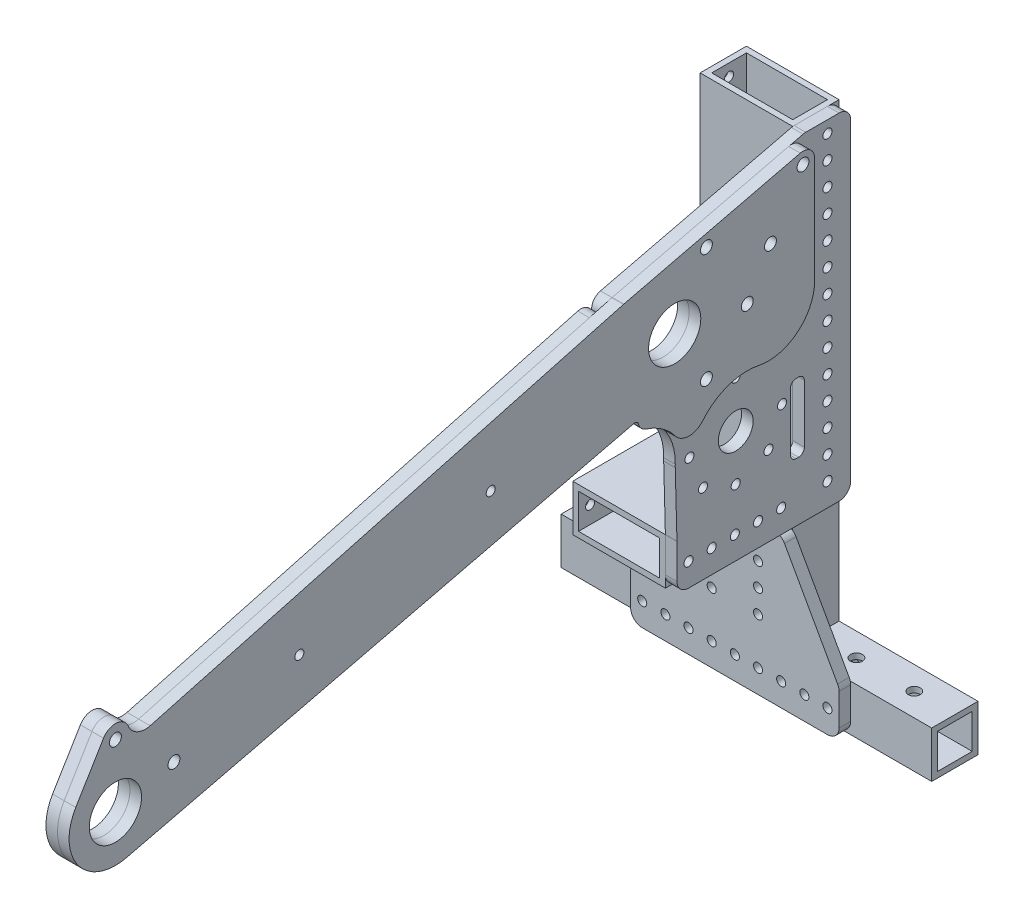
SolidWorks part; units mm, degrees
ref_plane "Alzado" through (0, 0, 0) normal (0, 0, 1) x (1, 0, 0)
ref_plane "Planta" through (0, 0, 0) normal (0, 1, 0) x (1, 0, 0)
ref_plane "Vista lateral" through (0, 0, 0) normal (1, 0, 0) x (0, 0, -1)
sketch "Croquis1" plane through (0, 0, 0) normal (0, 1, 0) x (1, 0, 0)
  line L1 (-101.6, -12.7) -> (101.6, -12.7)
  line L2 (-101.6, -12.7) -> (-101.6, 12.7)
  line L3 (-101.6, 12.7) -> (101.6, 12.7)
  line L4 (101.6, -12.7) -> (101.6, 12.7)
  line L5 (-101.6, -12.7) -> (101.6, 12.7) construction
  line L6 (-101.6, 12.7) -> (101.6, -12.7) construction
  point P0 (0, 0)
  dimension "D1" = 25.4
  dimension "D2" = 203.2
extrude "Saliente-Extruir1" add sketch "Croquis1" along normal blind 25.4
shell "Vaciado1" thickness 3.175 removed face at (-101.6, 12.7, 0) removed face at (101.6, 12.7, 0)
sketch "Croquis2" plane through (0, 25.4, 0) normal (0, 1, 0) x (1, 0, 0)
  line L0 (101.6, 12.7) -> (-101.6, 12.7) construction
  line L1 (-25.4, -12.7) -> (25.4, -12.7)
  line L2 (-25.4, -12.7) -> (-25.4, 12.7)
  line L3 (-25.4, 12.7) -> (25.4, 12.7)
  line L4 (25.4, -12.7) -> (25.4, 12.7)
  line L5 (-25.4, -12.7) -> (25.4, 12.7) construction
  line L6 (-25.4, 12.7) -> (25.4, -12.7) construction
  line L8 (-22.225, -9.525) -> (22.225, -9.525)
  line L9 (-22.225, -9.525) -> (-22.225, 9.525)
  line L10 (-22.225, 9.525) -> (22.225, 9.525)
  line L11 (22.225, -9.525) -> (22.225, 9.525)
  line L12 (-22.225, -9.525) -> (22.225, 9.525) construction
  line L13 (-22.225, 9.525) -> (22.225, -9.525) construction
  point P0 (0, 0)
  point P8 (0, 0)
  dimension "D1" = 50.8
  dimension "D2" = 3.175
  dimension "D3" = 3.175
extrude "Saliente-Extruir2" add sketch "Croquis2" along normal blind 247.65 separate body
sketch "Croquis3" plane through (0, 25.4, 0) normal (0, 1, 0) x (1, 0, 0)
  line L0 (0, 0) -> (0, 12.7) construction
  line L1 (25.4, 12.7) -> (-25.4, 12.7) construction
  circle A0 centre (-47.625, 0) radius 3.2639
  circle A1 centre (-79.375, 0) radius 3.2639
  circle A2 centre (79.375, 0) radius 3.2639
  circle A3 centre (47.625, 0) radius 3.2639
  dimension "D1" = 47.625
  dimension "D2" = 6.5278
  dimension "D3" = 31.75
extrude "Cortar-Extruir1" cut sketch "Croquis3" against normal through all
sketch "Croquis4" plane through (0, 0, 12.7) normal (0, 0, 1) x (1, 0, 0)
  line L0 (0, 25.4) -> (0, 139.6619) construction
  line L1 (-101.6, 25.4) -> (101.6, 25.4) construction
  line L2 (0, 139.6619) -> (-23.8125, 139.6619) construction
  circle A0 centre (0, 139.6619) radius 14.3129
  circle A1 centre (0, 139.6619) radius 23.8125 construction
  circle A2 centre (-23.8125, 139.6619) radius 2.4892 construction
  circle A3 centre (-11.9062, 160.2841) radius 2.4892
  circle A4 centre (11.9063, 160.2841) radius 2.4892
  circle A5 centre (23.8125, 139.6619) radius 2.4892 construction
  circle A6 centre (11.9062, 119.0397) radius 2.4892
  circle A7 centre (-11.9063, 119.0397) radius 2.4892
  dimension "D1" = 28.6258
  dimension "D3" = 47.625
  dimension "D4" = 4.9784
  dimension "D2" = 114.2619
  dimension "D6" = 23.8125
  dimension "D5" = 6
extrude "Cortar-Extruir2" cut sketch "Croquis4" against normal through all
sketch "Croquis8" plane through (0, 0, 12.7) normal (0, 0, 1) x (1, 0, 0)
  line L0 (0, 0) -> (0, 273.05) construction
  line L1 (-101.6, 12.7) -> (0, 12.7) construction
  line L2 (-101.6, 25.4) -> (-101.6, 0) construction
  line L3 (0, 12.7) -> (-12.7, 12.7) construction
  line L4 (0, 12.7) -> (12.7, 12.7) construction
  line L5 (-25.4, 273.05) -> (25.4, 273.05) construction
  line L6 (-12.7, 12.7) -> (-12.7, 25.4) construction
  circle A0 centre (0, 12.7) radius 2.4892
  circle A1 centre (-12.7, 12.7) radius 2.4892
  circle A2 centre (-25.4, 12.7) radius 2.4892
  circle A3 centre (-38.1, 12.7) radius 2.4892
  circle A4 centre (-50.8, 12.7) radius 2.4892
  circle A5 centre (0, 12.7) radius 2.4892
  circle A6 centre (-12.7, 12.7) radius 2.4892
  circle A7 centre (-25.4, 12.7) radius 2.4892
  circle A8 centre (-38.1, 12.7) radius 2.4892
  circle A9 centre (12.7, 12.7) radius 2.4892
  circle A10 centre (0, 12.7) radius 2.4892
  circle A11 centre (-12.7, 12.7) radius 2.4892
  circle A12 centre (-25.4, 12.7) radius 2.4892
  circle A13 centre (25.4, 12.7) radius 2.4892
  circle A14 centre (12.7, 12.7) radius 2.4892
  circle A15 centre (0, 12.7) radius 2.4892
  circle A16 centre (-12.7, 12.7) radius 2.4892
  circle A17 centre (38.1, 12.7) radius 2.4892
  circle A18 centre (25.4, 12.7) radius 2.4892
  circle A19 centre (12.7, 12.7) radius 2.4892
  circle A20 centre (0, 12.7) radius 2.4892
  circle A21 centre (12.7, 12.7) radius 2.4892
  circle A22 centre (25.4, 12.7) radius 2.4892
  circle A23 centre (38.1, 12.7) radius 2.4892
  circle A24 centre (50.8, 12.7) radius 2.4892
  circle A25 centre (-12.7, 25.4) radius 2.4892 [skipped]
  circle A26 centre (12.7, 25.4) radius 2.4892 [skipped]
  circle A27 centre (-12.7, 38.1) radius 2.4892
  circle A28 centre (12.7, 38.1) radius 2.4892
  circle A29 centre (-12.7, 50.8) radius 2.4892
  circle A30 centre (12.7, 50.8) radius 2.4892
  circle A31 centre (-12.7, 63.5) radius 2.4892
  circle A32 centre (12.7, 63.5) radius 2.4892
  circle A33 centre (-12.7, 76.2) radius 2.4892
  circle A34 centre (12.7, 76.2) radius 2.4892
  dimension "D1" = 4.9784
  dimension "D4" = 12.7
  dimension "D5" = 12.7
  dimension "D7" = 12.7
  dimension "D2" = 5
  dimension "D3" = 5
  dimension "D6" = 6
extrude "Cortar-Extruir4" cut sketch "Croquis8" against normal through all contours A4 | A3 | A2 | A1 | A0 | A9 | A13 | A17 | A24 | A28 | A29 | A30 | A31 | A32 | A34 | A33 | A27 region at (0, 12.7, 12.7) region at (-12.7, 12.7, 12.7) region at (-25.4, 12.7, 12.7) region at (-38.1, 12.7, 12.7) region at (-50.8, 12.7, 12.7) region at (12.7, 12.7, 12.7) region at (25.4, 12.7, 12.7) region at (38.1, 12.7, 12.7) region at (50.8, 12.7, 12.7) region at (12.7, 38.1, 12.7) region at (-12.7, 50.8, 12.7) region at (12.7, 50.8, 12.7) region at (-12.7, 63.5, 12.7) region at (12.7, 63.5, 12.7) region at (-12.7, 76.2, 12.7) region at (12.7, 76.2, 12.7)
sketch "Croquis6" plane through (0, 0, 12.7) normal (0, 0, 1) x (1, 0, 0)
  line L0 (25.4, 273.05) -> (25.4, 25.4) construction
  line L1 (-25.4, 88.646) -> (25.4, 88.646)
  line L2 (-25.4, 88.646) -> (-25.4, 114.046)
  line L3 (-25.4, 114.046) -> (25.4, 114.046)
  line L4 (25.4, 88.646) -> (25.4, 114.046)
  line L5 (-25.4, 88.646) -> (25.4, 114.046) construction
  line L6 (-25.4, 114.046) -> (25.4, 88.646) construction
  line L7 (-101.6, 25.4) -> (101.6, 25.4) construction
  line L9 (-22.225, 91.821) -> (22.225, 91.821)
  line L10 (-22.225, 91.821) -> (-22.225, 110.871)
  line L11 (-22.225, 110.871) -> (22.225, 110.871)
  line L12 (22.225, 91.821) -> (22.225, 110.871)
  line L13 (-22.225, 91.821) -> (22.225, 110.871) construction
  line L14 (-22.225, 110.871) -> (22.225, 91.821) construction
  point P0 (0, 101.346)
  point P11 (0, 101.346)
  dimension "D1" = 25.4
  dimension "D2" = 63.246
  dimension "D3" = 3.175
  dimension "D4" = 3.175
extrude "Saliente-Extruir3" add sketch "Croquis6" along normal blind 69.85 separate body
sketch "Croquis7" plane through (0, 114.046, 0) normal (0, 1, 0) x (1, 0, 0)
  line L0 (0, -12.7) -> (0, -82.55) construction
  line L1 (-25.4, -12.7) -> (25.4, -12.7) construction
  line L2 (25.4, -82.55) -> (-25.4, -82.55) construction
  line L3 (16.51, -12.7) -> (-16.51, -12.7)
  line L4 (25.4, -12.7) -> (-25.4, -12.7) construction
  line L5 (-16.51, -12.7) -> (-16.51, -34.798)
  line L6 (-13.208, -38.1) -> (13.208, -38.1)
  line L7 (16.51, -12.7) -> (16.51, -34.798)
  arc A0 (16.51, -34.798) -> (13.208, -38.1) centre (13.208, -34.798) cw
  arc A1 (-16.51, -34.798) -> (-13.208, -38.1) centre (-13.208, -34.798) ccw
  point P12 (0, -38.1)
  point P16 (16.51, -38.1)
  point P19 (-16.51, -38.1)
  dimension "D3" = 3.302
  dimension "D1" = 25.4
  dimension "D2" = 33.02
extrude "Cortar-Extruir3" cut sketch "Croquis7" against normal up to next (3.175 mm away)
sketch "Croquis11" plane through (25.4, 0, 0) normal (1, 0, 0) x (0, 0, -1)
  line L0 (0, -101.854) -> (-381, -101.854) construction
  line L1 (-82.55, 88.646) -> (-82.55, 114.046) construction
  line L2 (-82.55, 88.646) -> (-12.7, 88.646) construction
  line L6 (-517.96, -101.854) -> (-276.66, -101.854) construction
  line L7 (-517.96, -101.854) -> (-517.96, 139.446) construction
  line L8 (-517.96, 139.446) -> (-276.66, 139.446) construction
  line L9 (-276.66, -101.854) -> (-276.66, 139.446) construction
  circle A0 centre (-396.875, 145.796) radius 38.1
  dimension "D3" = 76.2
  dimension "D4" = 209.55
  dimension "D5" = 276.225
  dimension "D1" = 190.5
  dimension "D2" = 381
  dimension "D6" = 241.3
sketch "Croquis9" plane through (0, 0, 12.7) normal (0, 0, 1) x (1, 0, 0)
  line L0 (0, 0) -> (0, 273.05) construction
  line L1 (-25.4, 273.05) -> (25.4, 273.05) construction
  line L2 (50.8, 0) -> (-50.8, 0)
  line L3 (-101.6, 0) -> (101.6, 0) construction
  line L4 (-57.15, 6.35) -> (-57.15, 23.7481)
  line L5 (-101.6, 25.4) -> (101.6, 25.4) construction
  line L6 (-56.3451, 26.8425) -> (-27.2168, 79.0403)
  line L7 (-25.4, 273.05) -> (-25.4, 25.4) construction
  line L8 (-21.6717, 82.296) -> (21.6717, 82.296)
  line L9 (56.3451, 26.8425) -> (27.2168, 79.0403)
  line L10 (57.15, 6.35) -> (57.15, 23.7481)
  line L11 (-25.4, 88.646) -> (25.4, 88.646) construction
  circle A0 centre (-50.8, 12.7) radius 2.4892 construction
  arc A2 (-50.8, 0) -> (-57.15, 6.35) centre (-50.8, 6.35) cw
  arc A3 (-57.15, 23.7481) -> (-56.3451, 26.8425) centre (-50.8, 23.7481) cw
  arc A4 (-27.2168, 79.0403) -> (-21.6717, 82.296) centre (-21.6717, 75.946) cw
  arc A5 (27.2168, 79.0403) -> (21.6717, 82.296) centre (21.6717, 75.946) ccw
  arc A6 (57.15, 23.7481) -> (56.3451, 26.8425) centre (50.8, 23.7481) ccw
  arc A7 (50.8, 0) -> (57.15, 6.35) centre (50.8, 6.35) ccw
  circle A9 centre (-25.4, 12.7) radius 2.4892
  circle A10 centre (-25.4, 12.7) radius 2.4892
  circle A11 centre (-12.7, 12.7) radius 2.4892
  circle A12 centre (-12.7, 12.7) radius 2.4892
  circle A13 centre (0, 12.7) radius 2.4892
  circle A14 centre (0, 12.7) radius 2.4892
  circle A15 centre (0, 12.7) radius 2.4892
  circle A16 centre (0, 12.7) radius 2.4892
  circle A17 centre (12.7, 12.7) radius 2.4892
  circle A18 centre (12.7, 12.7) radius 2.4892
  circle A19 centre (-38.1, 12.7) radius 2.4892
  circle A20 centre (-38.1, 12.7) radius 2.4892
  circle A21 centre (-25.4, 12.7) radius 2.4892
  circle A22 centre (-25.4, 12.7) radius 2.4892
  circle A23 centre (-12.7, 12.7) radius 2.4892
  circle A24 centre (-12.7, 12.7) radius 2.4892
  circle A25 centre (0, 12.7) radius 2.4892
  circle A26 centre (0, 12.7) radius 2.4892
  circle A27 centre (-50.8, 12.7) radius 2.4892
  circle A28 centre (-50.8, 12.7) radius 2.4892
  circle A29 centre (-38.1, 12.7) radius 2.4892
  circle A30 centre (-38.1, 12.7) radius 2.4892
  circle A31 centre (25.4, 12.7) radius 2.4892
  circle A32 centre (25.4, 12.7) radius 2.4892
  circle A33 centre (38.1, 12.7) radius 2.4892
  circle A34 centre (38.1, 12.7) radius 2.4892
  circle A35 centre (-12.7, 12.7) radius 2.4892
  circle A36 centre (-12.7, 12.7) radius 2.4892
  circle A37 centre (0, 12.7) radius 2.4892
  circle A38 centre (0, 12.7) radius 2.4892
  circle A39 centre (12.7, 12.7) radius 2.4892
  circle A40 centre (12.7, 12.7) radius 2.4892
  circle A41 centre (25.4, 12.7) radius 2.4892
  circle A42 centre (25.4, 12.7) radius 2.4892
  circle A43 centre (-25.4, 12.7) radius 2.4892
  circle A44 centre (-25.4, 12.7) radius 2.4892
  circle A45 centre (-12.7, 12.7) radius 2.4892
  circle A46 centre (-12.7, 12.7) radius 2.4892
  circle A47 centre (50.8, 12.7) radius 2.4892
  circle A48 centre (50.8, 12.7) radius 2.4892
  circle A49 centre (38.1, 12.7) radius 2.4892
  circle A50 centre (38.1, 12.7) radius 2.4892
  circle A51 centre (25.4, 12.7) radius 2.4892
  circle A52 centre (25.4, 12.7) radius 2.4892
  circle A53 centre (12.7, 12.7) radius 2.4892
  circle A54 centre (12.7, 12.7) radius 2.4892
  circle A55 centre (0, 12.7) radius 2.4892
  circle A56 centre (0, 12.7) radius 2.4892
  circle A57 centre (12.7, 12.7) radius 2.4892
  circle A58 centre (12.7, 12.7) radius 2.4892
  circle A59 centre (-12.7, 76.2) radius 2.4892
  circle A60 centre (-12.7, 76.2) radius 2.4892
  circle A61 centre (12.7, 63.5) radius 2.4892
  circle A62 centre (12.7, 63.5) radius 2.4892
  circle A63 centre (-12.7, 63.5) radius 2.4892
  circle A64 centre (-12.7, 63.5) radius 2.4892
  circle A65 centre (12.7, 50.8) radius 2.4892
  circle A66 centre (12.7, 50.8) radius 2.4892
  circle A67 centre (-12.7, 50.8) radius 2.4892
  circle A68 centre (-12.7, 50.8) radius 2.4892
  circle A69 centre (12.7, 38.1) radius 2.4892
  circle A70 centre (12.7, 38.1) radius 2.4892
  circle A71 centre (-12.7, 38.1) radius 2.4892
  circle A72 centre (-12.7, 38.1) radius 2.4892
  circle A73 centre (12.7, 76.2) radius 2.4892
  circle A74 centre (12.7, 76.2) radius 2.4892
  point P22 (-57.15, 0)
  point P25 (-57.15, 25.4)
  point P28 (-25.4, 82.296)
  point P38 (0, 82.296)
  circle M37 centre (-50.8, 12.7) radius 2.4892
  circle M38 centre (-38.1, 12.7) radius 2.4892
  circle M39 centre (-25.4, 12.7) radius 2.4892
  circle M40 centre (-12.7, 12.7) radius 2.4892
  circle M41 centre (0, 12.7) radius 2.4892
  circle M42 centre (12.7, 12.7) radius 2.4892
  circle M43 centre (25.4, 12.7) radius 2.4892
  circle M44 centre (38.1, 12.7) radius 2.4892
  circle M45 centre (50.8, 12.7) radius 2.4892
  line M46 (-101.6, 0) -> (101.6, 0)
  line M48 (101.6, 25.4) -> (-101.6, 25.4)
  dimension "D1" = 6.35
  dimension "D3" = 6.35
  dimension "D37" = 6.35
  dimension "D4" = 0
  dimension "D5" = 0
  dimension "D6" = 0
  dimension "D7" = 0
  dimension "D8" = 0
  dimension "D9" = 0
  dimension "D10" = 0
  dimension "D11" = 0
  dimension "D12" = 0
  dimension "D13" = 0
  dimension "D14" = 0
  dimension "D15" = 0
  dimension "D16" = 0
  dimension "D17" = 0
  dimension "D18" = 0
  dimension "D19" = 0
  dimension "D20" = 0
  dimension "D21" = 0
  dimension "D22" = 0
  dimension "D23" = 0
  dimension "D24" = 0
  dimension "D25" = 0
  dimension "D26" = 0
  dimension "D27" = 0
  dimension "D28" = 0
  dimension "D29" = 0
  dimension "D30" = 0
  dimension "D31" = 0
  dimension "D32" = 0
  dimension "D33" = 0
  dimension "D34" = 0
  dimension "D35" = 0
  dimension "D36" = 0
extrude "Saliente-Extruir4" add sketch "Croquis9" along normal blind 6.35 separate body contours L0 L8 A4 L6 A3 A60 A64 A68 A72 M48 | L0 A6 L9 A5 L8 A74 A70 A66 A62 M48 | L0 A3 L4 A2 M46 M41 M48 M37 M39 M40 M38 | L0 L2 A7 L10 A6 A56 M48 M42 M44 M45 M43 region at (-28.4143, 12.7709, 12.7) region at (28.4143, 12.7709, 12.7) region at (-21.9575, 49.932, 12.7) region at (21.9575, 49.932, 12.7)
sketch "Croquis15" plane through (25.4, 0, 0) normal (1, 0, 0) x (0, 0, -1)
  line L0 (-12.7, 0) -> (-12.7, 171.1325) construction
  line L1 (-12.7, 273.05) -> (-12.7, 25.4) construction
  line L2 (-72.5746, 227.1642) -> (-41.5317, 154.1315) construction
  line L3 (-105.4538, 208.2656) -> (-57.9713, 144.6822) construction
  line L4 (-94.6246, 238.2605) -> (-401.3483, 164.3633) construction
  line L5 (-392.4017, 127.2287) -> (-85.6779, 201.1258) construction
  line L8 (-82.55, 114.046) -> (-12.7, 114.046) construction
  circle A0 centre (-50.32, 150.396) radius 30
  arc A1 (-57.9713, 144.6822) -> (-41.5317, 154.1315) centre (-50.32, 150.396) ccw construction
  arc A2 (-401.3483, 164.3633) -> (-392.4017, 127.2287) centre (-396.875, 145.796) ccw construction
  arc A3 (-72.5746, 227.1642) -> (-105.4538, 208.2656) centre (-90.1513, 219.6932) ccw construction
  arc A4 (-85.6779, 201.1258) -> (-94.6246, 238.2605) centre (-90.1513, 219.6932) ccw construction
  dimension "D2" = 60
  dimension "D3" = 19.0986
  dimension "D4" = 38.1972
  dimension "D1" = 171.1325
  dimension "D7" = 6.35
  dimension "D8" = 7.62
sketch "Croquis16" plane through (25.4, 0, 0) normal (1, 0, 0) x (0, 0, -1)
  line L0 (-50.32, 150.396) -> (-50.32, 175.796) construction
  line L1 (-13.4332, 272.8734) -> (-118.1525, 247.644)
  line L2 (-82.55, 94.996) -> (-82.55, 113.9625)
  line L3 (-82.5522, 114.1295) -> (-83.4835, 149.5234)
  line L4 (-76.2, 88.646) -> (6.35, 88.646)
  line L5 (12.7, 273.05) -> (12.7, 25.4) construction
  line L6 (12.7, 94.996) -> (12.7, 266.7)
  line L7 (6.35, 273.05) -> (-11.9459, 273.05)
  line L8 (-94.6246, 238.2605) -> (-401.3483, 164.3633) construction
  line L9 (-122.8385, 239.9833) -> (-110.0117, 186.743)
  line L10 (-90.1513, 219.6932) -> (-116.4251, 213.3632) construction
  circle A0 centre (-90.1513, 219.6932) radius 14.3256
  circle A1 centre (-50.32, 150.396) radius 33.175
  circle A4 centre (-50.32, 150.396) radius 9.5631
  circle A5 centre (-50.32, 150.396) radius 25.4 construction
  circle A6 centre (-50.32, 175.796) radius 2.4892
  circle A7 centre (-32.3595, 168.3565) radius 2.4892 construction
  circle A8 centre (-24.92, 150.396) radius 2.4892
  circle A9 centre (-32.3595, 132.4355) radius 2.4892
  circle A10 centre (-50.32, 124.996) radius 2.4892
  circle A11 centre (-68.2805, 132.4355) radius 2.4892
  circle A12 centre (-75.72, 150.396) radius 2.4892
  circle A13 centre (-68.2805, 168.3565) radius 2.4892
  arc A18 (-105.7366, 182.1707) -> (-83.4864, 151.1506) centre (-115.2282, 151.8727) cw
  arc A19 (-110.0117, 186.743) -> (-105.7366, 182.1707) centre (-103.8383, 188.2304) ccw
  arc A21 (-118.1525, 247.644) -> (-122.8385, 239.9833) centre (-116.6652, 241.4706) ccw
  arc A23 (-11.9459, 273.05) -> (-13.4332, 272.8734) centre (-11.9459, 266.7) ccw
  circle A26 centre (-50.32, 150.396) radius 30 construction
  arc A29 (-82.55, 113.9625) -> (-82.5522, 114.1295) centre (-88.9, 113.9625) ccw
  arc A31 (12.7, 266.7) -> (6.35, 273.05) centre (6.35, 266.7) ccw
  arc A32 (6.35, 88.646) -> (12.7, 94.996) centre (6.35, 94.996) ccw
  arc A33 (-82.55, 94.996) -> (-76.2, 88.646) centre (-76.2, 94.996) ccw
  point P45 (-12.7, 273.05)
  point P72 (-82.55, 114.046)
  point P74 (12.7, 273.05)
  point P77 (12.7, 88.646)
  point P80 (-82.55, 88.646)
  line M2 (12.7, 25.4) -> (12.7, 273.05)
  line M3 (12.7, 273.05) -> (-12.7, 273.05)
  line M4 (-12.7, 273.05) -> (-12.7, 25.4)
  dimension "D1" = 28.6512
  dimension "D2" = 3.175
  dimension "D3" = 31.75
  dimension "D4" = 19.1262
  dimension "D5" = 50.8
  dimension "D6" = 4.9784
  dimension "D9" = 6.35
  dimension "D10" = 6.35
  dimension "D14" = 6.35
  dimension "D15" = 6.35
  dimension "D12" = 6.35
  dimension "D8" = 25.4
  dimension "D11" = 12.7
  dimension "D7" = 8
extrude "Saliente-Extruir5" add sketch "Croquis16" along normal blind 6.35 separate body contours L4 A32 A31 A23 M2 M3 M4 | L2 A33 L4 A23 L1 A21 L9 A19 A18 A1 L3 A29 A0 M4 | A1 A13 A12 A11 A10 A9 A8 A6 A4 region at (25.4, 191.9467, 55.8371) region at (25.4, 180.8478, 0.0418) region at (25.4, 182.6306, 49.9534)
sketch "Croquis12" plane through (25.4, 0, 0) normal (1, 0, 0) x (0, 0, -1)
  line L0 (-82.55, 101.346) -> (-12.7, 101.346) construction
  line L1 (-82.55, 88.646) -> (-82.55, 114.046) construction
  line L2 (-12.7, 88.646) -> (-12.7, 114.046) construction
  line L3 (0, 273.05) -> (0, 0) construction
  line L4 (-12.7, 273.05) -> (12.7, 273.05) construction
  line L5 (0, 101.346) -> (-12.7, 101.346) construction
  line L6 (0, 101.346) -> (0, 114.046) construction
  circle A1 centre (0, 101.346) radius 2.4892
  circle A2 centre (-12.7, 101.346) radius 2.4892 [skipped]
  circle A3 centre (-25.4, 101.346) radius 2.4892
  circle A4 centre (-38.1, 101.346) radius 2.4892
  circle A5 centre (-50.8, 101.346) radius 2.4892
  circle A6 centre (0, 114.046) radius 2.4892
  circle A7 centre (0, 126.746) radius 2.4892
  circle A8 centre (0, 139.446) radius 2.4892
  circle A9 centre (0, 152.146) radius 2.4892
  circle A10 centre (0, 164.846) radius 2.4892
  circle A11 centre (0, 177.546) radius 2.4892
  circle A12 centre (0, 190.246) radius 2.4892
  circle A13 centre (0, 202.946) radius 2.4892
  circle A14 centre (0, 215.646) radius 2.4892
  circle A15 centre (0, 228.346) radius 2.4892
  circle A16 centre (0, 241.046) radius 2.4892
  circle A17 centre (0, 253.746) radius 2.4892
  circle A18 centre (0, 266.446) radius 2.4892
  circle A19 centre (-63.5, 101.346) radius 2.4892
  circle A20 centre (-76.2, 101.346) radius 2.4892
  dimension "D1" = 4.9784
  dimension "D3" = 12.7
  dimension "D5" = 12.7
  dimension "D2" = 7
  dimension "D4" = 14
extrude "Cortar-Extruir5" cut sketch "Croquis12" against normal through all and the other way through all
sketch "Croquis17" plane through (31.75, 0, 0) normal (1, 0, 0) x (0, 0, -1)
  line L0 (-403.5186, 170.3118) -> (-118.2389, 247.6205)
  line L1 (-118.0654, 247.6649) -> (-21.2705, 270.9852)
  line L2 (-390.9258, 121.1026) -> (-118.1525, 186.8202)
  line L3 (-392.4017, 127.2287) -> (-85.6779, 201.1258) construction
  line L4 (-118.1525, 186.8202) -> (-112.4025, 188.2055)
  line L5 (-13.4332, 206.3797) -> (-13.4332, 264.8118)
  line L7 (-403.3993, 184.1476) -> (-418.6226, 158.9186)
  circle A0 centre (-396.875, 145.796) radius 14.3256
  circle A1 centre (-90.1513, 219.6932) radius 14.3256
  circle A2 centre (-396.875, 145.796) radius 25.4
  arc A3 (-118.2389, 247.6205) -> (-118.0654, 247.6649) centre (-116.578, 241.4916) cw
  arc A4 (-21.2705, 270.9852) -> (-13.4332, 264.8118) centre (-19.7832, 264.8118) cw
  arc A5 (-13.4332, 206.3797) -> (-43.9384, 181.4981) centre (-38.8332, 206.3797) cw
  circle A6 centre (-50.32, 150.396) radius 31.75
  arc A8 (-110.0117, 186.743) -> (-105.7366, 182.1707) centre (-103.8383, 188.2304) ccw construction
  arc A9 (-110.0117, 186.743) -> (-105.7366, 182.1707) centre (-103.8383, 188.2304) ccw
  arc A10 (-110.0117, 186.743) -> (-112.4025, 188.2055) centre (-111.9383, 186.2789) ccw
  arc A11 (-83.4864, 151.1506) -> (-105.7366, 182.1707) centre (-115.2282, 151.8727) ccw construction
  arc A12 (-89.8175, 170.9084) -> (-105.7366, 182.1707) centre (-115.2282, 151.8727) ccw
  arc A13 (-89.8175, 170.9084) -> (-74.8387, 170.5677) centre (-82.1943, 176.6192) ccw
  circle A14 centre (-396.875, 180.2108) radius 7.62
  arc A16 (-389.8471, 183.1558) -> (-377.8191, 177.2761) centre (-380.4766, 187.0824) ccw
  point P19 (-118.1525, 247.644)
  point P23 (-13.4332, 272.8734)
  line M28 (-13.4332, 272.8734) -> (-118.1525, 247.644)
  arc M29 (-118.1525, 247.644) -> (-122.8385, 239.9833) centre (-116.6652, 241.4706) ccw
  line M30 (-122.8385, 239.9833) -> (-110.0117, 186.743)
  circle M38 centre (-90.1513, 219.6932) radius 14.3256
  dimension "D1" = 28.6512
  dimension "D2" = 50.8
  dimension "D3" = 6.35
  dimension "D4" = 63.5
  dimension "D5" = 9.525
  dimension "D6" = 25.4
  dimension "D7" = 15.24
  dimension "D8" = 34.4148
  dimension "D9" = 10.16
extrude "Saliente-Extruir6" add sketch "Croquis17" along normal blind 6.35 separate body contours A2 L2 L0 M30 M29 | L5 A4 A3 L0 M28 M29 M30 M38 | A2 A0 | A16 A14 L7 A2 L0 | A14 M30 region at (31.75, 173.536, 401.4081) region at (31.75, 184.8147, 244.5216) region at (31.75, 165.3985, 381.8776) region at (31.75, 220.7032, 61.6214) region at (31.75, 180.2108, 396.875)
sketch "Croquis18" plane through (38.1, 0, 0) normal (1, 0, 0) x (0, 0, -1)
  line L0 (-122.8385, 239.9833) -> (-110.0117, 186.743) construction
  line L1 (-122.754, 239.6323) -> (-111.9631, 194.8431)
  line L2 (-403.5186, 170.3118) -> (-118.2389, 247.6205) construction
  line L3 (-403.3993, 184.1476) -> (-418.6226, 158.9186) construction
  line L5 (-403.3993, 184.1476) -> (-418.6226, 158.9186)
  line L6 (-390.9258, 121.1026) -> (-118.1525, 186.8202) construction
  line L7 (-403.5186, 170.3118) -> (-130.5882, 244.274)
  line L10 (-122.8385, 239.9833) -> (-110.0117, 186.743) construction
  line L11 (-390.9258, 121.1026) -> (-116.6492, 187.1824)
  circle A1 centre (-396.875, 145.796) radius 25.4
  circle A2 centre (-396.875, 145.796) radius 25.4
  arc A3 (-116.6492, 187.1824) -> (-111.9631, 194.8431) centre (-118.1365, 193.3558) ccw
  circle A5 centre (-396.875, 145.796) radius 14.3256
  circle A6 centre (-396.875, 145.796) radius 14.3256
  arc A12 (-122.754, 239.6323) -> (-130.5882, 244.274) centre (-128.9273, 238.145) ccw
  arc A13 (-389.8471, 183.1558) -> (-377.8191, 177.2761) centre (-380.4766, 187.0824) ccw construction
  circle A14 centre (-396.875, 180.2108) radius 7.62 construction
  arc A15 (-389.8471, 183.1558) -> (-377.8191, 177.2761) centre (-380.4766, 187.0824) ccw
  circle A16 centre (-396.875, 180.2108) radius 7.62
  point P18 (-110.4758, 188.6697)
  line M10 (-118.2389, 247.6205) -> (-377.8191, 177.2761)
  arc M11 (-418.6226, 158.9186) -> (-390.9258, 121.1026) centre (-396.875, 145.796) ccw
  circle M13 centre (-396.875, 145.796) radius 14.3256
  line M33 (-403.3993, 184.1476) -> (-418.6226, 158.9186)
  arc M34 (-377.8191, 177.2761) -> (-389.8471, 183.1558) centre (-380.4766, 187.0824) cw
  arc M35 (-389.8471, 183.1558) -> (-403.3993, 184.1476) centre (-396.875, 180.2108) ccw
  dimension "D2" = 6.35
  dimension "D1" = 0
  dimension "D3" = 0
extrude "Saliente-Extruir7" add sketch "Croquis18" along normal blind 6.35 from surface separate body contours L1 A12 A2 A3 M10 | A2 M11 M13 | A16 A2 L7 M33 M34 | A16 M35 region at (38.1, 184.7417, 244.7476) region at (38.1, 173.536, 401.4081) region at (38.1, 131.2122, 416.7871) region at (38.1, 180.2108, 396.875) starting at face at (25.4, 101.346, -2.4892)
sketch "Croquis22" plane through (38.1, 0, 0) normal (1, 0, 0) x (0, 0, -1)
  line L0 (-396.875, 145.796) -> (-90.1513, 219.6932) construction
  line L1 (-90.1513, 219.6932) -> (-50.32, 150.396) construction
  line L4 (-50.32, 236.121) -> (-37.62, 236.121) construction
  line L5 (-21.2705, 270.9852) -> (-118.0654, 247.6649) construction
  circle A0 centre (-396.875, 180.2108) radius 3.2639
  circle A1 centre (-364.7735, 153.53) radius 3.2639
  circle A2 centre (-396.875, 145.796) radius 19.0986 construction
  arc A3 (-401.3483, 164.3633) -> (-392.4017, 127.2287) centre (-396.875, 145.796) ccw construction
  circle A4 centre (-364.7735, 153.53) radius 6.35 construction
  circle A7 centre (-72.747, 189.4137) radius 3.2639
  circle A8 centre (-72.747, 189.4137) radius 6.35 construction
  circle A9 centre (-50.32, 213.896) radius 6.35 construction
  circle A10 centre (-50.32, 213.896) radius 3.2639
  circle A13 centre (-37.62, 236.121) radius 3.2639
  circle A14 centre (-37.62, 236.121) radius 6.35 construction
  circle A15 centre (-72.747, 252.0515) radius 3.2639
  circle A16 centre (-72.747, 252.0515) radius 6.35 construction
  circle A17 centre (-19.7832, 264.8118) radius 6.35 construction
  circle A18 centre (-19.7832, 264.8118) radius 3.2639
  dimension "D1" = 6.5278
  dimension "D2" = 33.02
  dimension "D3" = 12.7
  dimension "D4" = 34.925
  dimension "D5" = 63.5
  dimension "D6" = 22.225
  dimension "D7" = 12.7
extrude "Cortar-Extruir6" cut sketch "Croquis22" against normal through all
sketch "Croquis24" plane through (38.1, 0, 0) normal (1, 0, 0) x (0, 0, -1)
  line L0 (-396.875, 145.796) -> (-90.1513, 219.6932) construction
  line L1 (-243.5131, 182.7446) -> (-247.9864, 201.3119) construction
  line L2 (-94.6246, 238.2605) -> (-401.3483, 164.3633) construction
  circle A0 centre (-295.9867, 170.1024) radius 2.4892
  circle A1 centre (-191.0395, 195.3867) radius 2.4892
  dimension "D1" = 4.9784
  dimension "D2" = 53.975
extrude "Cortar-Extruir7" cut sketch "Croquis24" against normal through all
sketch "Croquis25" plane through (31.75, 0, 0) normal (1, 0, 0) x (0, 0, -1)
  line L0 (-12.7, 0) -> (-12.7, 139.7) construction
  line L1 (-12.7, 123.825) -> (-12.7, 155.575)
  line L2 (-12.7, 0) -> (-12.7, 171.1325) construction
  line L3 (-15.875, 158.75) -> (-17.145, 158.75)
  line L4 (-20.32, 155.575) -> (-20.32, 123.825)
  line L5 (-12.7, 139.7) -> (-20.32, 139.7) construction
  line L6 (-15.875, 120.65) -> (-17.145, 120.65)
  arc A0 (-12.7, 155.575) -> (-15.875, 158.75) centre (-15.875, 155.575) ccw
  arc A1 (-15.875, 120.65) -> (-12.7, 123.825) centre (-15.875, 123.825) ccw
  arc A2 (-17.145, 120.65) -> (-20.32, 123.825) centre (-17.145, 123.825) cw
  arc A3 (-17.145, 158.75) -> (-20.32, 155.575) centre (-17.145, 155.575) ccw
  point P13 (-12.7, 158.75)
  point P16 (-12.7, 120.65)
  point P19 (-20.32, 120.65)
  point P22 (-20.32, 158.75)
  dimension "D4" = 3.175
  dimension "D1" = 139.7
  dimension "D2" = 7.62
  dimension "D3" = 38.1
extrude "Cortar-Extruir8" cut sketch "Croquis25" against normal through all
delete or keep bodies "Sólido-Eliminar/Conservar 1" [suppressed] type keep bodies bodies 112
delete or keep bodies "Sólido-Eliminar/Conservar 2" [suppressed] type keep bodies bodies 111
delete or keep bodies "Sólido-Eliminar/Conservar 3" [suppressed] type keep bodies bodies 107
delete or keep bodies "Sólido-Eliminar/Conservar 4" [suppressed] type keep bodies bodies 109
delete or keep bodies "Sólido-Eliminar/Conservar 5" [suppressed] type keep bodies bodies 121
delete or keep bodies "Sólido-Eliminar/Conservar 6" [suppressed] type keep bodies bodies 119
equation "\"D1@Croquis15\"=5.5500+1.1875pulgadas"
equation "\"D3@Croquis15\"=(12*5mm)/pi"
equation "\"D4@Croquis15\"=(24*5mm)/pi"
equation "\"D5@Croquis15\"=(50*5mm)+1mm"
equation "\"D6@Croquis15\"=(150*5mm)+1mm"
